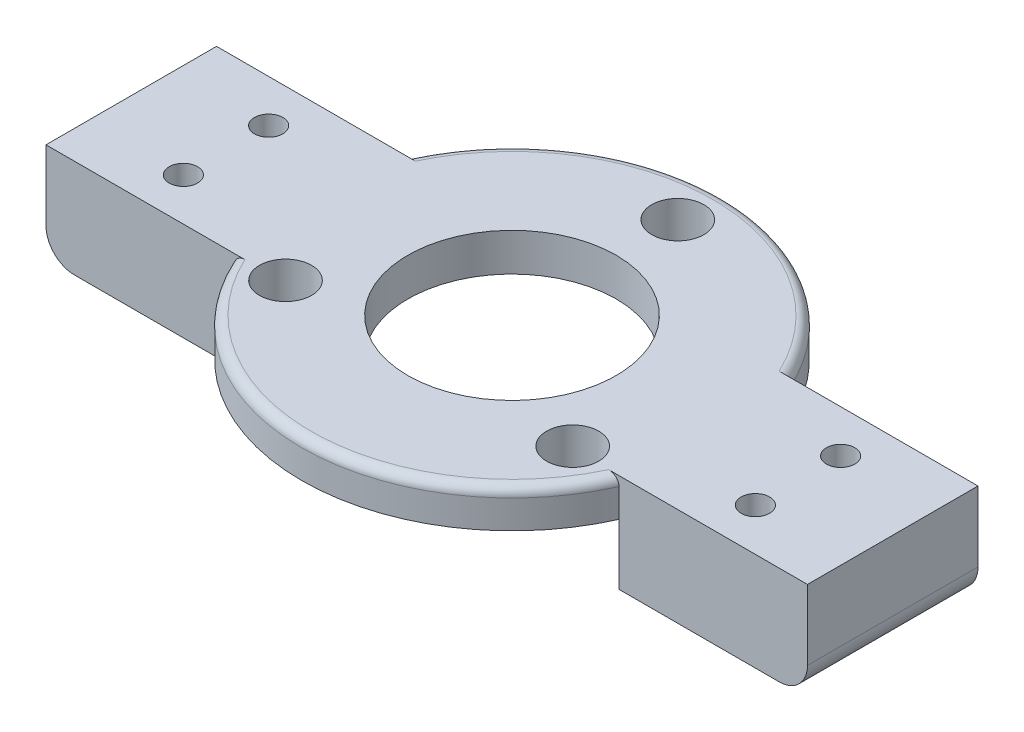
SolidWorks part; units mm, degrees
ref_plane "Front Plane" through (0, 0, 0) normal (0, 0, 1) x (1, 0, 0)
ref_plane "Top Plane" through (0, 0, 0) normal (0, 1, 0) x (1, 0, 0)
ref_plane "Right Plane" through (0, 0, 0) normal (1, 0, 0) x (0, 0, -1)
sketch "Sketch1" plane through (0, 0, 0) normal (0, 1, 0) x (1, 0, 0)
  circle A0 centre (0, 0) radius 17.45
  circle A1 centre (0, 0) radius 12.45
  dimension "D1" = 5
  dimension "D2" = 34.9
extrude "Boss-Extrude1" add sketch "Sketch1" along normal blind 8
sketch "Sketch2" plane through (0, 8, 0) normal (0, 1, 0) x (1, 0, 0)
  circle A0 centre (0, 0) radius 12.45
  circle A1 centre (0, 0) radius 20
  dimension "D1" = 40
extrude "Boss-Extrude2" add sketch "Sketch2" along normal blind 2
sketch "Sketch3" plane through (0, 10, 0) normal (0, 1, 0) x (1, 0, 0)
  circle A0 centre (0, 0) radius 12.45
  circle A1 centre (0, 0) radius 32.5
  dimension "D1" = 65
extrude "Boss-Extrude3" add sketch "Sketch3" along normal blind 4
fillet "Fillet1" radius 1 1 edges at (0, 14, 32.5)
sketch "Sketch10" plane through (0, 14, 0) normal (0, 1, 0) x (1, 0, 0)
  line L1 (30.1869, 9) -> (40.1869, 9)
  line L2 (30.1869, 9) -> (30.1869, -9)
  line L3 (30.1869, -9) -> (40.1869, -9)
  line L4 (40.1869, 9) -> (40.1869, -9)
  line L5 (-30.1869, 9) -> (-40.1869, 9)
  line L6 (-30.1869, 9) -> (-30.1869, -9)
  line L7 (-30.1869, -9) -> (-40.1869, -9)
  line L8 (-40.1869, 9) -> (-40.1869, -9)
  circle A0 centre (0, 0) radius 31.5 construction
  dimension "D1" = 10
  dimension "D2" = 18
extrude "Boss-Extrude6" add sketch "Sketch10" along normal offset from surface (4 mm away) 4 from surface up to face at (0, 10, 20) starting at face at (0, 10, 20)
sketch "Sketch4" plane through (0, 14, 0) normal (0, 1, 0) x (1, 0, 0)
  line L0 (34.1869, 0) -> (-34.1869, 0) construction
  line L2 (-34.1869, 9) -> (-34.1869, -9)
  line L8 (34.1869, 9) -> (34.1869, -9)
  line L10 (34.1869, 9) -> (40.1869, 9)
  line L11 (40.1869, 9) -> (40.1869, -9)
  line L12 (40.1869, -9) -> (34.1869, -9)
  line L13 (-34.1869, 9) -> (-40.1869, 9)
  line L14 (-40.1869, 9) -> (-40.1869, -9)
  line L15 (-40.1869, -9) -> (-34.1869, -9)
  point P8 (0, 0)
  dimension "D1" = 6
extrude "Boss-Extrude4" add sketch "Sketch4" along normal blind 75 and the other way blind 4
sketch "Sketch5" plane through (34.1869, 0, 0) normal (-1, 0, 0) x (0, 0, 1)
  line L0 (-9, 14) -> (9, 14) construction
  line L1 (-9, 89) -> (9, 89) construction
  circle A0 centre (0, 79) radius 5.05
  point P7 (0, 89)
  dimension "D1" = 10.1
  dimension "D2" = 65
extrude "Cut-Extrude1" cut sketch "Sketch5" against normal blind 113 and the other way blind 306
sketch "Sketch6" plane through (0, 0, -9) normal (0, 0, -1) x (-1, 0, 0)
  line L1 (34.1869, 75.95) -> (40.1869, 75.95)
  line L2 (34.1869, 75.95) -> (34.1869, 65.95)
  line L3 (34.1869, 65.95) -> (40.1869, 65.95)
  line L4 (40.1869, 75.95) -> (40.1869, 65.95)
  line L6 (40.1869, 89) -> (40.1869, 10) construction
  line L7 (34.1869, 14) -> (34.1869, 89) construction
  dimension "D1" = 10
  dimension "D2" = 8
extrude "Boss-Extrude5" add sketch "Sketch6" along normal blind 15 and the other way blind 32.85
sketch "Sketch7" plane through (-34.1869, 0, 0) normal (1, 0, 0) x (0, 0, -1)
  line L0 (-17.5, 71) -> (17.5, 71) construction
  circle A0 centre (-17.5, 71) radius 1.6292
  circle A1 centre (17.5, 71) radius 1.5803
  circle A3 centre (0, 79) radius 4.05 construction
  point P6 (0, 71)
  dimension "D2" = 8
  dimension "D1" = 35
  dimension "D3" = 17.5
extrude "Cut-Extrude2" cut sketch "Sketch7" against normal blind 10
sketch "Sketch9" plane through (-34.1869, 0, 0) normal (1, 0, 0) x (0, 0, -1)
  circle A0 centre (0, 79) radius 5.05
  dimension "D1" = 10.1
extrude "Cut-Extrude3" cut sketch "Sketch9" against normal blind 10 and the other way blind 10
sketch "Sketch11" plane through (34.1869, 0, 0) normal (-1, 0, 0) x (0, 0, 1)
  line L0 (-9, 14) -> (9, 14) construction
  line L1 (4.8913, 14) -> (-4.8913, 14)
  line L2 (4.8913, 14) -> (4.8913, 17.2345)
  line L3 (4.8913, 17.2345) -> (-4.8913, 17.2345)
  line L4 (-4.8913, 14) -> (-4.8913, 17.2345)
  line L5 (9, 10) -> (-9, 10) construction
  point P6 (0, 14)
  point P9 (0, 10)
extrude "Cut-Extrude4" cut sketch "Sketch11" against normal blind 61 and the other way blind 123
fillet "Fillet4" radius 3 6 edges at (-37.1869, 65.95, 23.85) (-37.1869, 75.95, 23.85) (-37.1869, 65.95, -24) (-37.1869, 75.95, -24) (-37.1869, 89, 9) (-37.1869, 89, -9)
fillet "Fillet5" radius 3 2 edges at (40.1869, 10, 0) (-40.1869, 10, 0)
sketch "Sketch12" plane through (40.1869, 0, 0) normal (1, 0, 0) x (0, 0, -1)
  line L0 (9, 10) -> (-9, 10) construction
  line L1 (41.8928, 10) -> (-66.8986, 10)
  line L2 (41.8928, 10) -> (41.8928, -14.0418)
  line L3 (41.8928, -14.0418) -> (-66.8986, -14.0418)
  line L4 (-66.8986, 10) -> (-66.8986, -14.0418)
extrude "Cut-Extrude5" cut sketch "Sketch12" against normal blind 110.678
sketch "Sketch15" plane through (0, 14, 0) normal (0, 1, 0) x (1, 0, 0)
  circle A0 centre (0, 0) radius 22
  dimension "D1" = 44
extrude "Cut-Extrude7" cut sketch "Sketch15" against normal blind 4
sketch "Sketch13" plane through (0, 14, 0) normal (0, 1, 0) x (1, 0, 0)
  line L0 (-15.1554, -8.75) -> (0, 17.5) construction
  line L1 (0, 17.5) -> (15.1554, -8.75) construction
  line L2 (15.1554, -8.75) -> (-15.1554, -8.75) construction
  circle A0 centre (0, 0) radius 11
  circle A1 centre (0, 0) radius 22
  circle A2 centre (0, 0) radius 17.5 construction
  circle A3 centre (0, 17.5) radius 2.75
  circle A4 centre (-15.1554, -8.75) radius 2.75
  circle A5 centre (15.1554, -8.75) radius 2.75
  dimension "D1" = 22
  dimension "D2" = 5.5
  dimension "D3" = 44
  dimension "D5" = 35
  dimension "D4" = 60
extrude "Boss-Extrude7" add sketch "Sketch13" against normal blind 4
fillet "Fillet6" radius 3 2 edges at (37.1869, 89, -9) (37.1869, 89, 9)
sketch "Sketch16" plane through (0, 10, 0) normal (0, -1, 0) x (1, 0, 0)
  line L0 (-31.229, 9) -> (-20.2938, 9)
  line L1 (31.229, 9) -> (20.2938, 9)
  arc A0 (-31.229, 9) -> (31.229, 9) centre (0, 0) cw
  arc A1 (-20.2938, 9) -> (20.2938, 9) centre (0, 0) cw
  dimension "D1" = 22.2
extrude "Cut-Extrude8" cut sketch "Sketch16" against normal blind 5
mirror "Mirror1" about plane through (0, 0, 0) normal (0, 0, 1) of "Cut-Extrude8"
fillet "Fillet7" radius 1 2 edges at (0, 14, 22.2) (0, 14, -22.2)
sketch "Sketch17" plane through (0, 10, 0) normal (0, -1, 0) x (1, 0, 0)
  line L0 (20.2938, -9) -> (40.1869, -9)
  line L1 (40.1869, -9) -> (40.1869, 9)
  line L2 (40.1869, 9) -> (20.2938, 9)
  arc A0 (20.2938, -9) -> (20.2938, 9) centre (0, 0) ccw
  arc A1 (-20.2938, -9) -> (20.2938, -9) centre (0, 0) ccw construction
extrude "Boss-Extrude8" add sketch "Sketch17" along normal blind 6.4 and the other way blind 3
fillet "Fillet8" radius 3 1 edges at (40.1869, 3.6, 0)
mirror "Mirror2" about plane through (0, 0, 0) normal (1, 0, 0) of "Fillet8", "Boss-Extrude8"
sketch "Sketch21" plane through (40.1869, 0, 0) normal (1, 0, 0) x (0, 0, -1)
  circle A0 centre (0, 79) radius 6.05
  dimension "D1" = 12.1
extrude "Cut-Extrude12" cut sketch "Sketch21" along normal blind 3.8 from surface starting at face at (34.1869, 79, 5.05)
sketch "Sketch18" plane through (40.1869, 0, 0) normal (1, 0, 0) x (0, 0, -1)
  line L1 (44.3735, 99.3869) -> (-44.3735, 99.3869)
  line L2 (44.3735, 99.3869) -> (44.3735, 79)
  line L3 (44.3735, 79) -> (-44.3735, 79)
  line L4 (-44.3735, 99.3869) -> (-44.3735, 79)
  circle A0 centre (0, 79) radius 5.05 construction
  point P4 (0, 79)
extrude "Cut-Extrude9" cut sketch "Sketch18" against normal blind 10
sketch "Sketch19" plane through (0, 79, 0) normal (0, 1, 0) x (1, 0, 0)
  line L0 (40.1869, -9) -> (40.1869, -5.05) construction
  line L1 (34.1869, -6.05) -> (40.1869, -6.05)
  line L2 (34.1869, -6.05) -> (34.1869, -16.5)
  line L3 (34.1869, -16.5) -> (40.1869, -16.5)
  line L4 (40.1869, -6.05) -> (40.1869, -16.5)
  line L5 (34.1869, 6.05) -> (40.1869, 6.05)
  line L6 (34.1869, 6.05) -> (34.1869, 16.5)
  line L7 (34.1869, 16.5) -> (40.1869, 16.5)
  line L8 (40.1869, 6.05) -> (40.1869, 16.5)
  dimension "D1" = 33
extrude "Boss-Extrude9" add sketch "Sketch19" against normal blind 5
fillet "Fillet9" radius 2 2 edges at (37.1869, 74, -16.5) (37.1869, 74, 16.5)
sketch "Sketch22" plane through (-34.1869, 0, 0) normal (1, 0, 0) x (0, 0, -1)
  line L1 (-15.9989, 68.4) -> (-14.4978, 71)
  line L2 (-14.4978, 71) -> (-15.9989, 73.6)
  line L3 (-15.9989, 73.6) -> (-19.0011, 73.6)
  line L4 (-19.0011, 73.6) -> (-20.5022, 71)
  line L5 (-20.5022, 71) -> (-19.0011, 68.4)
  line L6 (-19.0011, 68.4) -> (-15.9989, 68.4)
  line L7 (20.5022, 71) -> (19.0011, 73.6)
  line L8 (19.0011, 73.6) -> (15.9989, 73.6)
  line L9 (15.9989, 73.6) -> (14.4978, 71)
  line L10 (14.4978, 71) -> (15.9989, 68.4)
  line L11 (15.9989, 68.4) -> (19.0011, 68.4)
  line L12 (19.0011, 68.4) -> (20.5022, 71)
  circle A0 centre (-17.5, 71) radius 2.6 construction
  circle A1 centre (17.5, 71) radius 2.6 construction
  dimension "D1" = 5.2
extrude "Cut-Extrude13" cut sketch "Sketch22" against normal blind 2
sketch "Sketch23" plane through (0, 79, 0) normal (0, 1, 0) x (1, 0, 0)
  line L0 (37.1869, -12.3) -> (37.1869, 12.3) construction
  line L1 (34.1869, -16.5) -> (40.1869, -16.5) construction
  line L2 (34.1869, -6.05) -> (34.1869, -16.5) construction
  circle A0 centre (37.1869, -12.3) radius 1
  circle A1 centre (37.1869, 12.3) radius 1
  point P4 (37.1869, 0)
  dimension "D1" = 2
  dimension "D2" = 4.2
  dimension "D3" = 3
extrude "Cut-Extrude14" cut sketch "Sketch23" against normal blind 11
sketch "Sketch24" plane through (0, 74, 0) normal (0, -1, 0) x (1, 0, 0)
  line L1 (37.1869, 9.9906) -> (39.1869, 11.1453)
  line L2 (39.1869, 11.1453) -> (39.1869, 13.4547)
  line L3 (39.1869, 13.4547) -> (37.1869, 14.6094)
  line L4 (37.1869, 14.6094) -> (35.1869, 13.4547)
  line L5 (35.1869, 13.4547) -> (35.1869, 11.1453)
  line L6 (35.1869, 11.1453) -> (37.1869, 9.9906)
  line L7 (37.1869, -14.6094) -> (39.1869, -13.4547)
  line L8 (39.1869, -13.4547) -> (39.1869, -11.1453)
  line L9 (39.1869, -11.1453) -> (37.1869, -9.9906)
  line L10 (37.1869, -9.9906) -> (35.1869, -11.1453)
  line L11 (35.1869, -11.1453) -> (35.1869, -13.4547)
  line L12 (35.1869, -13.4547) -> (37.1869, -14.6094)
  circle A0 centre (37.1869, 12.3) radius 2 construction
  circle A1 centre (37.1869, -12.3) radius 2 construction
  dimension "D1" = 4
extrude "Cut-Extrude16" cut sketch "Sketch24" against normal blind 1.7
sketch "Sketch26" plane through (0, 0, -9) normal (0, 0, -1) x (-1, 0, 0)
  line L1 (-69.4933, 100.5423) -> (66.966, 100.5423)
  line L2 (-69.4933, 100.5423) -> (-69.4933, 14)
  line L3 (-69.4933, 14) -> (66.966, 14)
  line L4 (66.966, 100.5423) -> (66.966, 14)
extrude "Cut-Extrude17" cut sketch "Sketch26" against normal blind 100 and the other way blind 100
sketch "Sketch27" plane through (0, 14, 0) normal (0, 1, 0) x (1, 0, 0)
  line L0 (30.1869, 4.5) -> (30.1869, -4.5) construction
  line L1 (40.1869, -9) -> (40.1869, 9) construction
  line L2 (-30.1869, 4.5) -> (-30.1869, -4.5) construction
  line L3 (-40.1869, 9) -> (-40.1869, -9) construction
  circle A0 centre (30.1869, -4.5) radius 1.5
  circle A1 centre (30.1869, 4.5) radius 1.5
  circle A2 centre (-30.1869, -4.5) radius 1.5
  circle A3 centre (-30.1869, 4.5) radius 1.5
  point P4 (30.1869, 0)
  point P7 (40.1869, 0)
  point P12 (-30.1869, 0)
  point P15 (-40.1869, 0)
  dimension "D2" = 3
  dimension "D1" = 9
  dimension "D3" = 9
  dimension "D5" = 10
  dimension "D6" = 10
extrude "Cut-Extrude18" cut sketch "Sketch27" against normal blind 100
sketch "Sketch28" plane through (0, 3.6, 0) normal (0, -1, 0) x (1, 0, 0)
  line L1 (27.0115, -4.5) -> (28.5992, -7.25)
  line L2 (28.5992, -7.25) -> (31.7746, -7.25)
  line L3 (31.7746, -7.25) -> (33.3623, -4.5)
  line L4 (33.3623, -4.5) -> (31.7746, -1.75)
  line L5 (31.7746, -1.75) -> (28.5992, -1.75)
  line L6 (28.5992, -1.75) -> (27.0115, -4.5)
  line L7 (27.0115, 4.5) -> (28.5992, 1.75)
  line L8 (28.5992, 1.75) -> (31.7746, 1.75)
  line L9 (31.7746, 1.75) -> (33.3623, 4.5)
  line L10 (33.3623, 4.5) -> (31.7746, 7.25)
  line L11 (31.7746, 7.25) -> (28.5992, 7.25)
  line L12 (28.5992, 7.25) -> (27.0115, 4.5)
  line L13 (-33.3623, 4.5) -> (-31.7746, 1.75)
  line L14 (-31.7746, 1.75) -> (-28.5992, 1.75)
  line L15 (-28.5992, 1.75) -> (-27.0115, 4.5)
  line L16 (-27.0115, 4.5) -> (-28.5992, 7.25)
  line L17 (-28.5992, 7.25) -> (-31.7746, 7.25)
  line L18 (-31.7746, 7.25) -> (-33.3623, 4.5)
  line L19 (-33.3623, -4.5) -> (-31.7746, -7.25)
  line L20 (-31.7746, -7.25) -> (-28.5992, -7.25)
  line L21 (-28.5992, -7.25) -> (-27.0115, -4.5)
  line L22 (-27.0115, -4.5) -> (-28.5992, -1.75)
  line L23 (-28.5992, -1.75) -> (-31.7746, -1.75)
  line L24 (-31.7746, -1.75) -> (-33.3623, -4.5)
  circle A0 centre (30.1869, -4.5) radius 2.75 construction
  circle A1 centre (30.1869, 4.5) radius 2.75 construction
  circle A2 centre (-30.1869, 4.5) radius 2.75 construction
  circle A3 centre (-30.1869, -4.5) radius 2.75 construction
  dimension "D1" = 5.5
extrude "Cut-Extrude19" cut sketch "Sketch28" against normal blind 5
